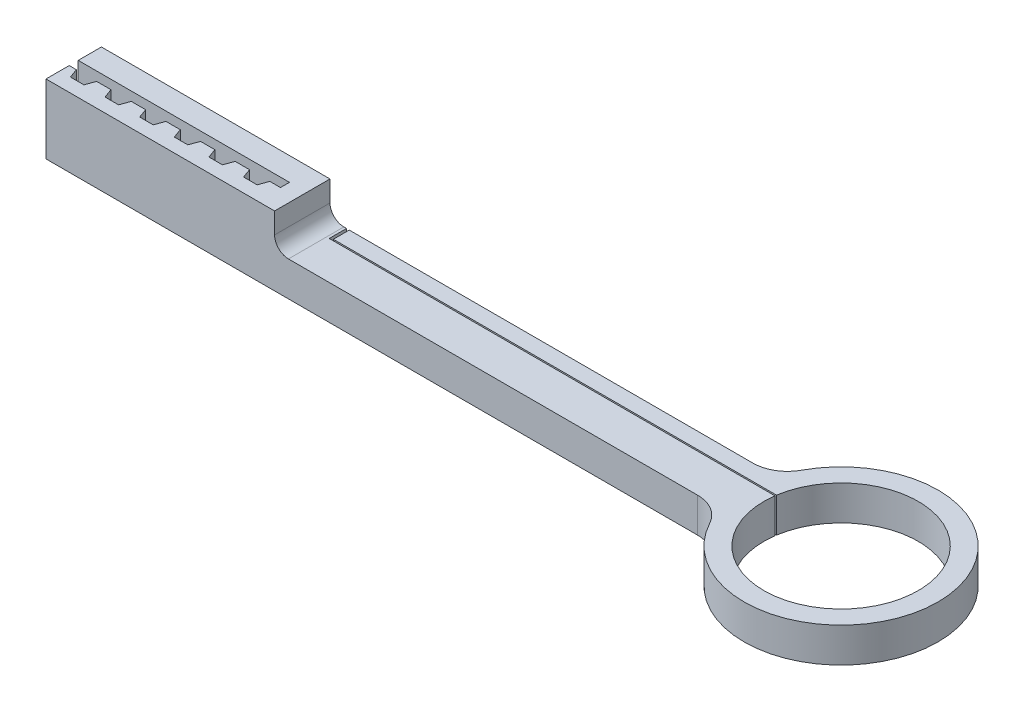
SolidWorks part; units mm, degrees
ref_plane "Спереди" through (0, 0, 0) normal (0, 0, 1) x (1, 0, 0)
ref_plane "Сверху" through (0, 0, 0) normal (0, 1, 0) x (1, 0, 0)
ref_plane "Справа" through (0, 0, 0) normal (1, 0, 0) x (0, 0, -1)
sketch "Эскиз1" plane through (0, 0, 0) normal (0, 1, 0) x (1, 0, 0)
  circle A0 centre (0, 0) radius 11.15
  circle A1 centre (0, 0) radius 14
  dimension "D1" = 22.3
  dimension "D2" = 28
extrude "ring" add sketch "Эскиз1" along normal blind 5
sketch "Эскиз2" plane through (0, 0, 0) normal (0, 1, 0) x (1, 0, 0)
  line L0 (34.0214, 0) -> (-42.1067, 0) construction
  line L1 (-10.7819, 4) -> (-10.7819, -4) construction
  line L2 (-10.7819, 4) -> (-110.7819, 4)
  line L4 (-10.7819, -4) -> (-110.7819, -4)
  line L5 (-110.7819, 4) -> (-110.7819, -4)
  circle A0 centre (0, 0) radius 11.5 construction
  arc A1 (-10.7819, 4) -> (-10.7819, -4) centre (0, 0) ccw
  point P9 (-10.7819, 0)
  dimension "D3" = 23
  dimension "D2" = 8
  dimension "D4" = 100
extrude "stick" add sketch "Эскиз2" along normal blind 5
sketch "Эскиз3" plane through (0, 0, 0) normal (0, 1, 0) x (1, 0, 0)
  line L0 (-110.7819, -4) -> (-13.4164, -4) construction
  line L1 (-110.7819, 4) -> (-77.7819, 4)
  line L2 (-110.7819, 4) -> (-110.7819, -4)
  line L3 (-110.7819, -4) -> (-77.7819, -4)
  line L4 (-77.7819, 4) -> (-77.7819, -4)
  dimension "D1" = 33
extrude "key" add sketch "Эскиз3" along normal blind 10
fillet "Скругление1" radius 5 2 edges at (-13.4164, 2.5, 4) (-13.4164, 2.5, -4)
ref_plane "Плоскость1" through (0, 2.5, 0) normal (0, 1, 0) x (-1, 0, 0)
sketch "Эскиз4" plane through (0, 2.5, 0) normal (0, 1, 0) x (1, 0, 0)
  line L0 (-110.7819, 0) -> (-77.7819, 0) construction
  line L1 (-110.7819, 4) -> (-110.7819, -4) construction
  line L2 (-77.7819, -4) -> (-77.7819, 4) construction
  line L3 (-110.7819, 0.65) -> (-80.2819, 0.65)
  line L4 (-109.2569, -2) -> (-107.3069, -2)
  line L5 (-109.5437, -0.65) -> (-90.7013, -0.65) construction
  line L6 (-109.7483, -0.65) -> (-109.2569, -2) construction
  line L7 (-109.7483, -0.65) -> (-109.2569, -2)
  line L8 (-107.3069, -2) -> (-106.8156, -0.65)
  line L9 (-108.2819, 0.7157) -> (-108.2819, -3.7603) construction
  line L10 (-109.7483, -0.65) -> (-110.7819, -0.65)
  line L11 (-106.8156, -0.65) -> (-105.7819, -0.65)
  line L12 (-110.7819, 0.65) -> (-110.7819, -0.65)
  line L13 (-104.7483, -0.65) -> (-105.7819, -0.65)
  line L14 (-104.2569, -2) -> (-102.3069, -2)
  line L15 (-102.3069, -2) -> (-101.8156, -0.65)
  line L16 (-101.8156, -0.65) -> (-100.7819, -0.65)
  line L17 (-104.7483, -0.65) -> (-104.2569, -2)
  line L18 (-99.7483, -0.65) -> (-100.7819, -0.65)
  line L19 (-99.2569, -2) -> (-97.3069, -2)
  line L20 (-97.3069, -2) -> (-96.8156, -0.65)
  line L21 (-96.8156, -0.65) -> (-95.7819, -0.65)
  line L22 (-99.7483, -0.65) -> (-99.2569, -2)
  line L23 (-110.7819, -4) -> (-77.7819, -4) construction
  line L24 (-94.7483, -0.65) -> (-95.7819, -0.65)
  line L25 (-94.2569, -2) -> (-92.3069, -2)
  line L26 (-92.3069, -2) -> (-91.8156, -0.65)
  line L27 (-91.8156, -0.65) -> (-90.7819, -0.65)
  line L28 (-94.7483, -0.65) -> (-94.2569, -2)
  line L43 (-89.7483, -0.65) -> (-90.7819, -0.65)
  line L44 (-89.2569, -2) -> (-87.3069, -2)
  line L45 (-87.3069, -2) -> (-86.8156, -0.65)
  line L46 (-86.8156, -0.65) -> (-85.7819, -0.65)
  line L47 (-89.7483, -0.65) -> (-89.2569, -2)
  line L48 (-84.7483, -0.65) -> (-85.7819, -0.65)
  line L49 (-84.2569, -2) -> (-82.3069, -2)
  line L50 (-82.3069, -2) -> (-81.8156, -0.65)
  line L51 (-81.8156, -0.65) -> (-80.7819, -0.65)
  line L52 (-84.7483, -0.65) -> (-84.2569, -2)
  line L53 (-80.7819, -0.65) -> (-80.2819, -0.65)
  line L54 (-80.2819, 0.65) -> (-80.2819, -0.65)
  point P12 (-108.2819, -2)
  dimension "D1" = 1.95
  dimension "D2" = 0.65
  dimension "D3" = 0.65
  dimension "D4" = 1.35
  dimension "D5" = 110
  dimension "D6" = 5
  dimension "D7" = 40
  dimension "D8" = 0.5
fillet "Скругление5" radius 2 1 edges at (-77.7819, 5, 0)
extrude "key hole" cut sketch "Эскиз4" against normal through all and the other way through all
sketch "Эскиз5" plane through (0, 0, 0) normal (0, -1, 0) x (1, 0, 0)
  line L0 (0, 0) -> (-70.3859, 0) construction
  line L1 (-75.4, -4) -> (-75.4, -1.5)
  line L3 (-75.4, -1.5) -> (0, -1.5)
  line L4 (0, -1.5) -> (0, -1.7)
  line L5 (0, -1.7) -> (-75, -1.7)
  line L6 (-75, -1.7) -> (-75, -4)
  line L7 (-75, -4) -> (-75.4, -4)
  line L8 (-16.7332, -4) -> (-110.7819, -4) construction
  dimension "D1" = 0.2
  dimension "D2" = 0.4
  dimension "D3" = 75
  dimension "D4" = 1.5
extrude "Вытянуть2" cut sketch "Эскиз5" against normal through all
